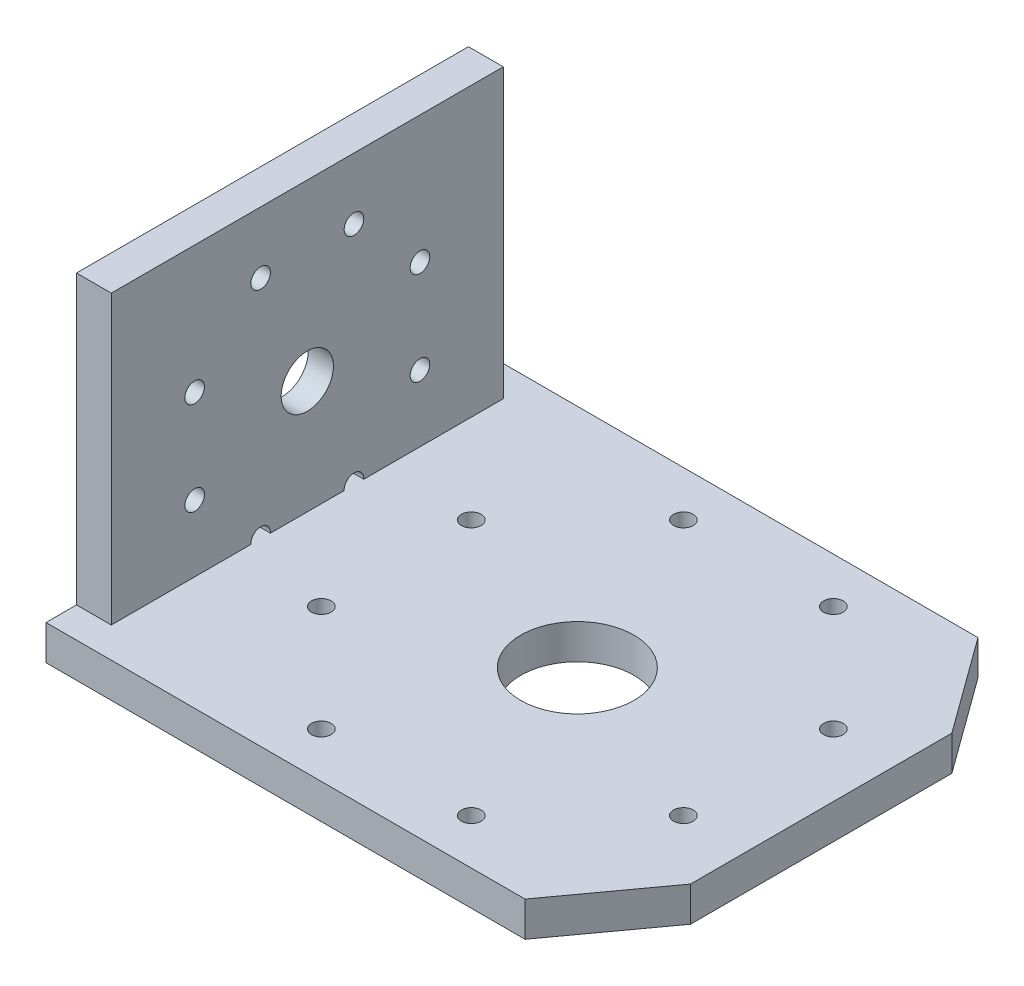
SolidWorks part; units mm, degrees
ref_plane "Front Plane" through (0, 0, 0) normal (0, 0, 1) x (1, 0, 0)
ref_plane "Top Plane" through (0, 0, 0) normal (0, 1, 0) x (1, 0, 0)
ref_plane "Right Plane" through (0, 0, 0) normal (1, 0, 0) x (0, 0, -1)
ref_plane "PL_Back_Plate_base" through (-70, 0, 0) normal (1, 0, 0) x (0, 0, -1)
sketch "SK_Back_Plate" plane through (-70, 0, 0) normal (1, 0, 0) x (0, 0, -1)
  line L0 (45, -34) -> (45, 40)
  line L1 (45, 40) -> (-45, 40)
  line L2 (-45, 40) -> (-45, -34)
  line L3 (-45, -34) -> (45, -34)
  circle A0 centre (25.8686, 10.7151) radius 2.25
  circle A1 centre (10.7151, 25.8686) radius 2.25
  circle A2 centre (-10.7151, 25.8686) radius 2.25
  circle A3 centre (-25.8686, 10.7151) radius 2.25
  circle A4 centre (-25.8686, -10.7151) radius 2.25
  circle A5 centre (-10.7151, -25.8686) radius 2.25
  circle A6 centre (10.7151, -25.8686) radius 2.25
  circle A7 centre (25.8686, -10.7151) radius 2.25
  circle A8 centre (0, 0) radius 6
  dimension "D9_SK_Back_Plate" = 4.5
  dimension "D12_SK_Back_Plate" = 4.5
  dimension "D15_SK_Back_Plate" = 4.5
  dimension "D18_SK_Back_Plate" = 4.5
  dimension "D21_SK_Back_Plate" = 4.5
  dimension "D24_SK_Back_Plate" = 4.5
  dimension "D27_SK_Back_Plate" = 4.5
  dimension "D30_SK_Back_Plate" = 4.5
  dimension "D33_SK_Back_Plate" = 12
  dimension "P1" = 45
  dimension "P2" = 34
  dimension "P3" = 45
  dimension "P4" = 40
  dimension "P5" = 45
  dimension "P6" = 40
  dimension "P7" = 45
  dimension "P8" = 34
  dimension "P10" = 25.8686
  dimension "P11" = 10.7151
  dimension "P13" = 10.7151
  dimension "P14" = 25.8686
  dimension "P16" = 10.7151
  dimension "P17" = 25.8686
  dimension "P19" = 25.8686
  dimension "P20" = 10.7151
  dimension "P22" = 25.8686
  dimension "P23" = 10.7151
  dimension "P25" = 10.7151
  dimension "P26" = 25.8686
  dimension "P28" = 10.7151
  dimension "P29" = 25.8686
  dimension "P31" = 25.8686
  dimension "P32" = 10.7151
extrude "Back_Plate" add sketch "SK_Back_Plate" along normal blind 8
ref_plane "PL_Roll_Pilot_Recess_base" through (-70, 0, 0) normal (1, 0, 0) x (0, 0, -1)
sketch "SK_Roll_Pilot_Recess" plane through (-70, 0, 0) normal (1, 0, 0) x (0, 0, -1)
  circle A0 centre (0, 0) radius 22.15
  dimension "D1_SK_Roll_Pilot_Recess" = 44.3
extrude "Roll_Pilot_Recess" cut sketch "SK_Roll_Pilot_Recess" along normal blind 2.2
ref_plane "PL_Medial_Plate_base" through (0, -34, 0) normal (0, 1, 0) x (1, 0, 0)
sketch "SK_Medial_Plate" plane through (0, -34, 0) normal (0, 1, 0) x (1, 0, 0)
  line L0 (-70, 52) -> (40, 52)
  line L1 (40, 52) -> (56, 30)
  line L2 (56, 30) -> (56, -30)
  line L3 (56, -30) -> (40, -52)
  line L4 (40, -52) -> (-70, -52)
  line L5 (-70, -52) -> (-70, 52)
  circle A0 centre (41.5746, 17.2208) radius 2.25
  circle A1 centre (17.2208, 41.5746) radius 2.25
  circle A2 centre (-17.2208, 41.5746) radius 2.25
  circle A3 centre (-41.5746, 17.2208) radius 2.25
  circle A4 centre (-41.5746, -17.2208) radius 2.25
  circle A5 centre (-17.2208, -41.5746) radius 2.25
  circle A6 centre (17.2208, -41.5746) radius 2.25
  circle A7 centre (41.5746, -17.2208) radius 2.25
  circle A8 centre (0, 0) radius 13
  dimension "D13_SK_Medial_Plate" = 4.5
  dimension "D16_SK_Medial_Plate" = 4.5
  dimension "D19_SK_Medial_Plate" = 4.5
  dimension "D22_SK_Medial_Plate" = 4.5
  dimension "D25_SK_Medial_Plate" = 4.5
  dimension "D28_SK_Medial_Plate" = 4.5
  dimension "D31_SK_Medial_Plate" = 4.5
  dimension "D34_SK_Medial_Plate" = 4.5
  dimension "D37_SK_Medial_Plate" = 26
  dimension "P1" = 70
  dimension "P2" = 52
  dimension "P3" = 40
  dimension "P4" = 52
  dimension "P5" = 56
  dimension "P6" = 30
  dimension "P7" = 56
  dimension "P8" = 30
  dimension "P9" = 40
  dimension "P10" = 52
  dimension "P11" = 70
  dimension "P12" = 52
  dimension "P14" = 41.5746
  dimension "P15" = 17.2208
  dimension "P17" = 17.2208
  dimension "P18" = 41.5746
  dimension "P20" = 17.2208
  dimension "P21" = 41.5746
  dimension "P23" = 41.5746
  dimension "P24" = 17.2208
  dimension "P26" = 41.5746
  dimension "P27" = 17.2208
  dimension "P29" = 17.2208
  dimension "P30" = 41.5746
  dimension "P32" = 17.2208
  dimension "P33" = 41.5746
  dimension "P35" = 41.5746
  dimension "P36" = 17.2208
extrude "Medial_Plate" add sketch "SK_Medial_Plate" along normal blind 8
equation "\"Roll_face_x\" = -70"
equation "\"Pitch_rear_y\" = -26"
